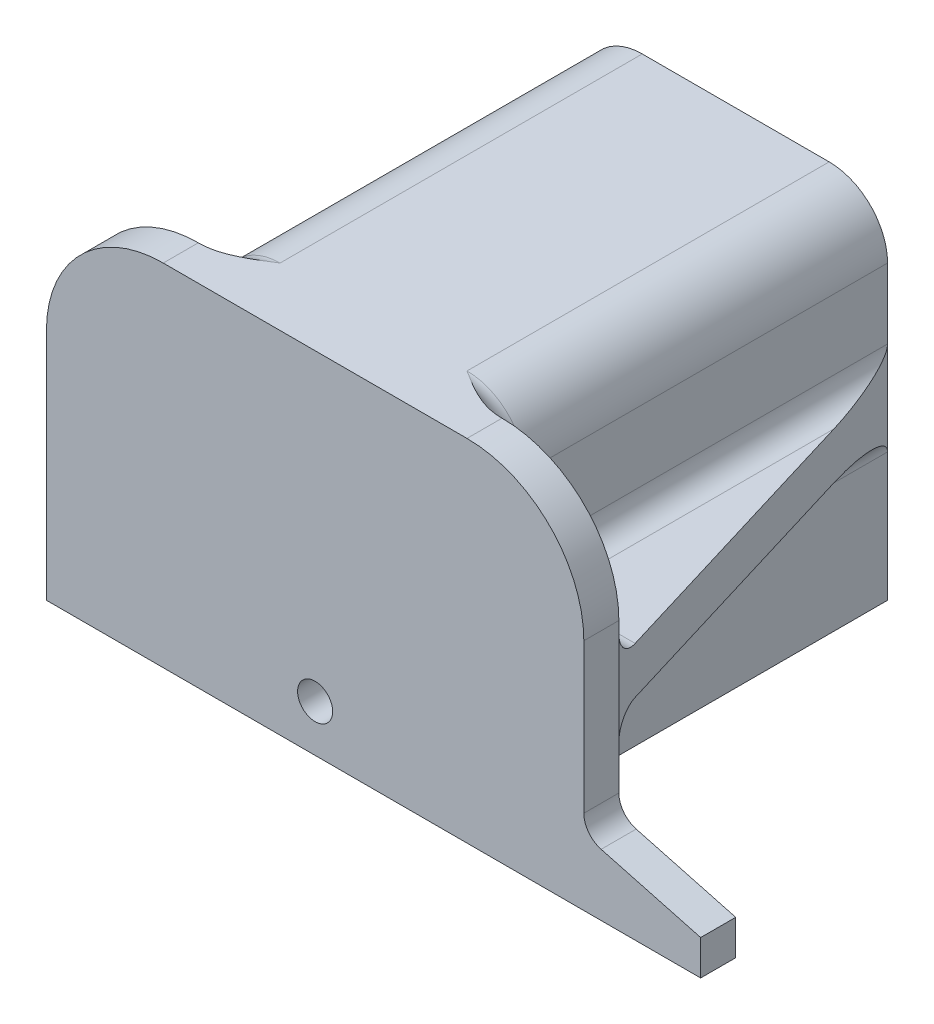
SolidWorks part; units mm, degrees
material "ABS"
ref_plane "Front Plane" through (0, 0, 0) normal (0, 0, 1) x (1, 0, 0)
ref_plane "Top Plane" through (0, 0, 0) normal (0, 1, 0) x (1, 0, 0)
ref_plane "Right Plane" through (0, 0, 0) normal (1, 0, 0) x (0, 0, -1)
sketch "Sketch1" plane through (0, 0, 0) normal (0, 1, 0) x (1, 0, 0)
  line L0 (0, 0) -> (0, -6) construction
  line L1 (10, 0) -> (-10, 0)
  line L2 (-10, 0) -> (-10, 30)
  line L3 (-10, 30) -> (-13, 30)
  line L4 (-23, -6) -> (-23, -3)
  line L5 (-23, -6) -> (23, -6)
  line L7 (-13, -3) -> (-13, 30)
  line L8 (-23, -3) -> (-13, -3)
  line L9 (23, -3) -> (13, -3)
  line L10 (13, -3) -> (13, 30)
  line L12 (23, -6) -> (23, -3)
  line L13 (10, 30) -> (13, 30)
  line L14 (10, 0) -> (10, 30)
  dimension "D1" = 10
  dimension "D2" = 30
  dimension "D3" = 6
  dimension "D4" = 3
  dimension "D5" = 10
  dimension "D6" = 3
extrude "Boss-Extrude1" add sketch "Sketch1" along normal mid plane 30
sketch "Sketch2" plane through (0, 0, 0) normal (0, 1, 0) x (1, 0, 0)
  line L0 (13, 30) -> (13, -3)
  line L1 (13, -3) -> (23, -3)
  line L2 (23, -3) -> (13, 30)
  point P3 (14.4577, 29.6016)
  point P4 (14.0578, 27.2123)
  point P6 (0, 0)
  point P8 (0, 0)
extrude "Boss-Extrude2" add sketch "Sketch2" along normal mid plane 4
mirror "Mirror1" about plane through (0, 0, 0) normal (1, 0, 0) of "Boss-Extrude2"
sketch "Sketch3" plane through (0, 0, 0) normal (0, 0, -1) x (-1, 0, 0)
  line L0 (0, 0) -> (0, -11) construction
  line L1 (0, -11) -> (0, -15) construction
  line L2 (-10, -15) -> (10, -15) construction
  circle A0 centre (0, -11) radius 1.5
  dimension "D2" = 3
  dimension "D1" = 4
extrude "Cut-Extrude1" cut sketch "Sketch3" against normal through all
fillet "Fillet1" radius 10 2 edges at (23, 15, 4.5) (-23, 15, 4.5)
sketch "Sketch4" plane through (0, 0, 0) normal (0, 0, -1) x (-1, 0, 0)
  line L0 (0, -15) -> (4, -15)
  line L1 (-10, -15) -> (10, -15) construction
  line L2 (4, -15) -> (4, -11)
  line L3 (0, -15) -> (-4, -15)
  line L4 (-4, -15) -> (-4, -11)
  circle A0 centre (0, -11) radius 4 construction
  arc A1 (4, -11) -> (-4, -11) centre (0, -11) ccw
  point P11 (0, 0)
  dimension "D1" = 8
extrude "Cut-Extrude4" cut sketch "Sketch4" against normal blind 2
fillet "Fillet2" radius 0.5 3 edges at (-4, -13, 2) (4, -13, 2) (0, -7, 2)
sketch "Sketch5" plane through (0, 0, 0) normal (0, 0, -1) x (-1, 0, 0)
  line L0 (-10, 15) -> (-10, -15) construction
  line L3 (10, 15) -> (-10, 15)
  line L7 (10, 15) -> (10, 12)
  line L8 (10, 12) -> (-10, 12)
  line L9 (-10, 15) -> (-10, 12)
  dimension "D1" = 3
extrude "Boss-Extrude3" add sketch "Sketch5" along normal up to surface (30 mm away) up to face at (-12, 0, -30)
sketch "Sketch6" plane through (23, 0, 0) normal (1, 0, 0) x (0, 0, -1)
  line L0 (-6, -15) -> (-3, -15)
  line L1 (-3, -15) -> (-3, -12)
  line L2 (-3, -2) -> (-3, -15) construction
  line L3 (-3, -12) -> (-6, -12)
  line L4 (-6, 5) -> (-6, -15) construction
  line L5 (-6, -12) -> (-6, -15)
extrude "Boss-Extrude4" add sketch "Sketch6" along normal blind 10
chamfer "Chamfer1" distance 10 angle 15 1 edges at (23, -12, 4.5) first distance on face at (28, -12, 4.5)
fillet "Fillet3" radius 5 5 edges at (0, 12, 0) (-10, 12, -15) (10, 12, -15) (-13, 15, -13.5) (13, 15, -13.5)
fillet "Fillet4" radius 2 15 edges at (-11.5355, 13.5355, 3) (11.5355, 13.5355, 3) (-13, -2, -13.5) (-18, -2, 3) (-18, 2, 3) (-13, 2, -13.5) (-13, 6, 3) (-13, -8.5, 3) (13, 6, 3) (13, -8.5, 3) (13, -2, -13.5) (18, -2, 3) (18, 2, 3) (13, 2, -13.5) (23, -9.3205, 4.5)
